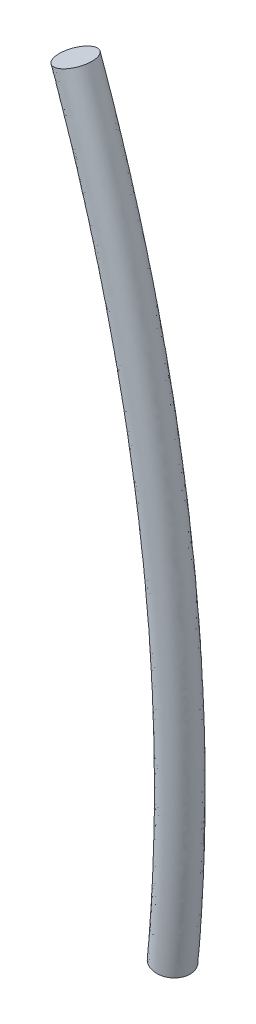
SolidWorks part; units mm, degrees
material "Custom Plastic"
ref_plane "X-Y Datum" through (0, 0, 0) normal (0, 0, 1) x (1, 0, 0)
ref_plane "X-Z Datum" through (0, 0, 0) normal (0, 1, 0) x (1, 0, 0)
ref_plane "Y-Z Datum" through (0, 0, 0) normal (1, 0, 0) x (0, 0, -1)
sketch3d "3DSketch1"
  line L1 (-135.4865, -165.0047, 234.086) -> (-135.4865, -141.5047, 234.086) construction
  circle A2 centre (-150.133, -40.3793, 237.2242) radius 2.286 construction
  spline S0 degree 2 poles (-150.133, -40.3793, 237.2242) (-128.4955, -106.7909, 235.6342) (-136.3601, -173.393, 233.8637) knots 0 0 0 1 1 1
  point P9 (-150.133, -42.6653, 237.2242)
sweep "Sweep1" add path "3DSketch1" circular profile diameter 6.35 parameters "D3"=6.35
